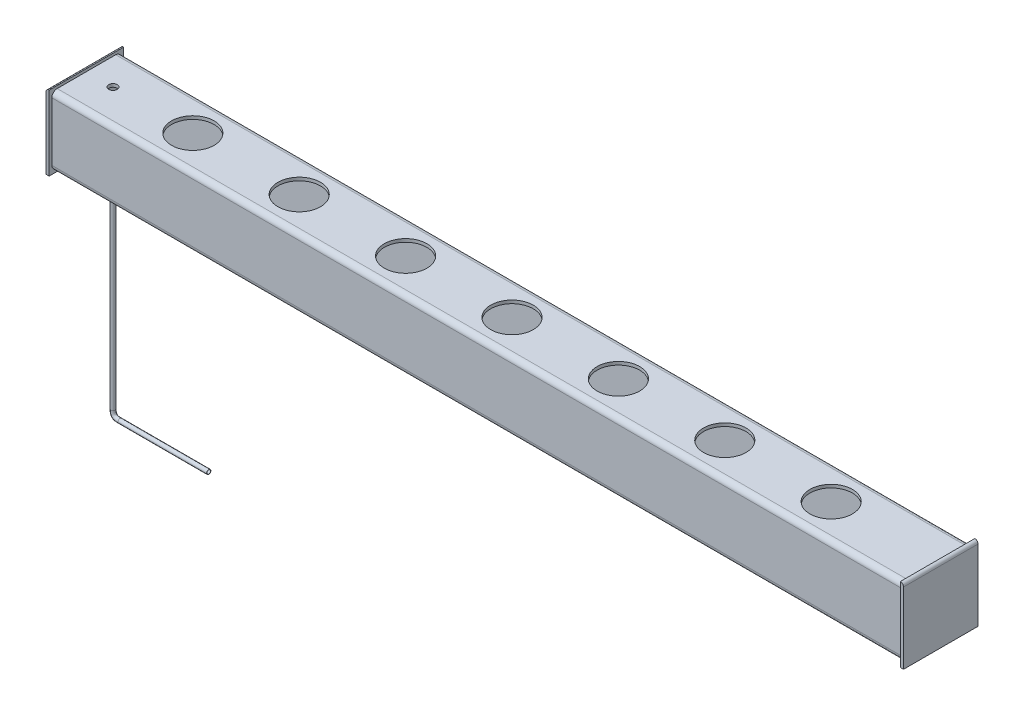
SolidWorks part; units mm, degrees
ref_plane "Front Plane" through (0, 0, 0) normal (0, 0, 1) x (1, 0, 0)
ref_plane "Top Plane" through (0, 0, 0) normal (0, 1, 0) x (1, 0, 0)
ref_plane "Right Plane" through (0, 0, 0) normal (1, 0, 0) x (0, 0, -1)
sketch "Sketch1" plane through (0, 0, 0) normal (1, 0, 0) x (0, 0, -1)
  line L1 (-32.5, -32.5) -> (32.5, -32.5)
  line L2 (-32.5, -32.5) -> (-32.5, 32.5)
  line L3 (-32.5, 32.5) -> (32.5, 32.5)
  line L4 (32.5, -32.5) -> (32.5, 32.5)
  line L5 (-32.5, -32.5) -> (32.5, 32.5) construction
  line L6 (-32.5, 32.5) -> (32.5, -32.5) construction
  point P0 (0, 0)
  dimension "D1" = 65
extrude "Boss-Extrude2" add sketch "Sketch1" along normal mid plane 800
fillet "Fillet1" radius 5 4 edges at (0, -32.5, -32.5) (0, -32.5, 32.5) (0, 32.5, -32.5) (0, 32.5, 32.5)
shell "Shell1" thickness 3 removed face at (-400, 0, 0) removed face at (400, 0, 0)
sketch "Sketch2" plane through (400, 0, 0) normal (1, 0, 0) x (0, 0, -1)
  line L1 (-35, -35) -> (35, -35)
  line L2 (-35, -35) -> (-35, 35)
  line L3 (-35, 35) -> (35, 35)
  line L4 (35, -35) -> (35, 35)
  line L5 (-35, -35) -> (35, 35) construction
  line L6 (-35, 35) -> (35, -35) construction
  point P0 (0, 0)
  dimension "D1" = 70
extrude "Boss-Extrude3" add sketch "Sketch2" along normal blind 3 separate body
fillet "Fillet4" radius 3 1 edges at (403, 35, 0)
mirror "Mirror1" about plane through (0, 0, 0) normal (1, 0, 0) of bodies 103
sketch "Sketch3" plane through (0, 32.5, 0) normal (0, 1, 0) x (1, 0, 0)
  circle A0 centre (0, 0) radius 20
  dimension "D1" = 40
extrude "Cut-Extrude1" cut sketch "Sketch3" against normal up to next (3 mm away)
pattern_linear "LPattern1" count 4 spacing 100 along (-1, 0, 0) count 4 spacing 100 along (1, 0, 0) of "Cut-Extrude1"
sketch "Sketch4" plane through (0, 32.5, 0) normal (0, 1, 0) x (1, 0, 0)
  circle A0 centre (-375, 0) radius 4
  circle A1 centre (-375, 0) radius 2
  circle A2 centre (-300, 0) radius 20 construction
  circle A3 centre (-375, 0) radius 1.75
  dimension "D1" = 8
  dimension "D2" = 4
  dimension "D3" = 75
  dimension "D4" = 0.25
extrude "Cut-Extrude2" cut sketch "Sketch4" against normal up to next (3 mm away) contours A1 | A0 A1 | A3 region at (-378.8869, 32.5, 0) region at (-376.9434, 32.5, 0) region at (-375, 32.5, 0)
extrude "Cut-Extrude3" cut sketch "Sketch4<3>" against normal through all contours A1
sketch "Sketch4<3>" plane through (0, 32.5, 0) normal (0, 1, 0) x (1, 0, 0) same geometry as "Sketch4"
extrude "Boss-Extrude4" add sketch "Sketch4<4>" along normal blind 10 and the other way blind 200 from surface separate body contours A1 A3 region at (-376.9434, 32.5, 0) starting at face at (-375, -29.5, 2)
sketch "Sketch4<4>" plane through (0, 32.5, 0) normal (0, 1, 0) x (1, 0, 0) same geometry as "Sketch4"
sketch "Sketch5" plane through (0, 0, 0) normal (0, 0, 1) x (1, 0, 0)
  line L0 (-375, -229.5) -> (-375, -235.8044) construction
  line L1 (-377, -229.5) -> (-373, -229.5) construction
  line L2 (-368.3029, -235.8044) -> (-285, -235.8044)
  line L3 (-364.6239, -235.8044) -> (-371.982, -235.8044) construction
  line L4 (-375, -232.8624) -> (-375, -225.775) construction
  line L5 (-375, -235.8044) -> (-368.3029, -235.8044) construction
  spline S0 degree 3 poles (-375, -229.5) (-375, -236.1071) (-371.3688, -235.8044) (-368.3029, -235.8044) knots 0 0 0 0 1 1 1 1
  dimension "D1" = 90
sketch "Sketch6" plane through (0, -229.5, 0) normal (0, -1, 0) x (1, 0, 0)
  circle A0 centre (-375, 0) radius 1.75 construction
  circle A1 centre (-375, 0) radius 2
  circle A2 centre (-375, 0) radius 2
  circle A3 centre (-375, 0) radius 1.75
  dimension "D1" = 0
sweep "Sweep1" add profiles "Sketch6" path "Sketch5"
